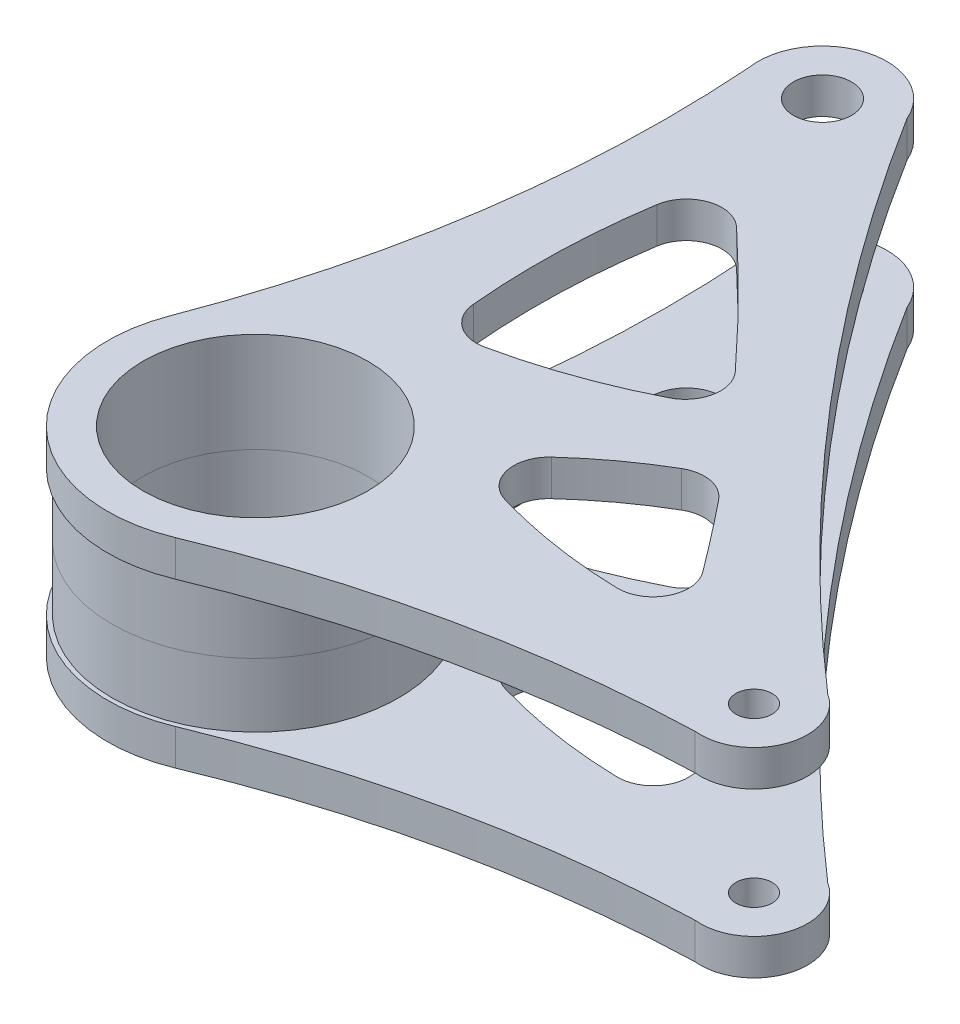
SolidWorks part; units mm, degrees
ref_plane "Front Plane" through (0, 0, 0) normal (0, 0, 1) x (1, 0, 0)
ref_plane "Top Plane" through (0, 0, 0) normal (0, 1, 0) x (1, 0, 0)
ref_plane "Right Plane" through (0, 0, 0) normal (1, 0, 0) x (0, 0, -1)
sketch "Sketch1" plane through (0, 0, 0) normal (0, 1, 0) x (1, 0, 0)
  line L0 (0, 80) -> (0, 0) construction
  line L1 (-9.0011, 81.338) -> (-20.6356, 3.0674)
  line L2 (6.9286, 85.8995) -> (74.8576, 6.1217)
  line L3 (4.3808, -20.3972) -> (70.6945, -6.1546)
  circle A0 centre (0, 0) radius 15.8623
  circle A1 centre (0, 80) radius 4.1
  circle A2 centre (69.1091, 1.2271) radius 2.55
  circle A3 centre (0, 80) radius 9.1
  circle A4 centre (0, 0) radius 20.8623
  circle A5 centre (69.1091, 1.2271) radius 7.55
  point P5 (0, 0)
  point P19 (59.8369, -10.5148)
  point P20 (60.48, 0)
  dimension "D1" = 8.2
  dimension "1" = 31.7246
  dimension "D3" = 5.1
  dimension "D5" = 69.12
  dimension "D4" = 80
  dimension "D6" = 5
extrude "Boss-Extrude1" add sketch "Sketch1" along normal blind 5.08 contours A1 A3 | A3 L0 A4 L3 A5 L2 | A4 A0 | L0 A3 L1 A4 | A5 A2 region at (-6.6966, 0, -74.2253) region at (29.5673, 0, -26.3622) region at (-7.9105, 0, -42.4424) region at (14.3346, 0, -14.3346) region at (75.994, 0, -3.7611)
sketch "Sketch3" plane through (0, 5.08, 0) normal (0, 1, 0) x (1, 0, 0)
  line L23 (6.9286, 85.8995) -> (74.8576, 6.1217) construction
  line L24 (6.9286, 85.8995) -> (74.8576, 6.1217)
  circle A29 centre (0, 80) radius 9.1
  circle A30 centre (0, 0) radius 20.8623
  circle A31 centre (69.1091, 1.2271) radius 7.55
  arc A32 (1.124, 24.8547) -> (31.4163, 35.8255) centre (-9.9767, 102.8121) ccw
  arc A33 (-9.1, 80) -> (-19.488, 7.4468) centre (-174.4184, 66.6496) cw
  arc A34 (7.9798, -19.2758) -> (68.3218, -6.2818) centre (73.7743, -178.2079) cw
  arc A35 (70.6945, -6.1546) -> (74.8576, 6.1217) centre (69.1091, 1.2271) ccw construction
  arc A36 (-20.6356, 3.0674) -> (4.3808, -20.3972) centre (0, 0) ccw construction
  arc A37 (6.9286, 85.8995) -> (-9.0011, 81.338) centre (0, 80) ccw construction
  arc A38 (3.0418, 64.268) -> (1.799, 20.7846) centre (102.9531, 39.6531) ccw
  arc A39 (3.0418, 64.268) -> (54.8896, 6.1217) centre (-221.7632, -188.3747) cw
  arc A40 (16.9411, 12.1752) -> (66.9551, 8.4633) centre (47.0346, 78.8536) ccw
  arc A41 (39.0442, 26.9044) -> (19.0809, 11.2502) centre (66.1753, -28.2515) ccw
  arc A42 (6.9286, 85.8995) -> (74.8576, 6.1217) centre (295.1167, 262.4762) ccw
  point P29 (3.0418, 64.268)
  point P32 (16.9411, 12.1752)
  point P36 (0, 0)
  point P40 (56.5898, 5.8028)
  point P41 (54.8896, 6.1217)
  line M15 (-9.0011, 81.338) -> (-20.6356, 3.0674)
  line M17 (4.3808, -20.3972) -> (70.6945, -6.1546)
  line M19 (74.8576, 6.1217) -> (6.9286, 85.8995)
extrude "Cut-Extrude1" cut sketch "Sketch3" against normal through all contours A33 A29 A30 M15 | A39 A29 A38 A32 | A39 A41 A40 | A34 A30 A31 M17 | A29 A42 A31 M19 region at (39.6539, 5.08, -44.9415) region at (-12.9781, 5.08, -42.6179) region at (38.0045, 5.08, 11.8867) region at (37.1781, 5.08, -14.1079) region at (11.4604, 5.08, -41.4426)
fillet "Fillet1" radius 5 6 edges at (54.8896, 2.54, -6.1217) (19.0809, 2.54, -11.2502) (39.0442, 2.54, -26.9044) (31.4163, 2.54, -35.8255) (1.124, 2.54, -24.8547) (3.0418, 2.54, -64.268)
sketch "Sketch2" plane through (0, 5.08, 0) normal (0, 1, 0) x (1, 0, 0)
  circle A7 centre (0, 0) radius 15.25
  circle A8 centre (0, 0) radius 20.25
  arc A9 (68.3218, -6.2818) -> (7.9798, -19.2758) centre (73.7743, -178.2079) ccw construction
  arc A10 (-19.488, 7.4468) -> (-8.994, 78.615) centre (-174.4184, 66.6496) ccw construction
  arc A11 (68.3218, -6.2818) -> (7.9798, -19.2758) centre (73.7743, -178.2079) ccw
  arc A12 (-19.488, 7.4468) -> (-8.994, 78.615) centre (-174.4184, 66.6496) ccw
  arc M7 (-19.488, 7.4468) -> (7.9798, -19.2758) centre (0, 0) ccw
  circle M14 centre (0, 0) radius 15.8623
extrude "Boss-Extrude2" add sketch "Sketch2" along normal blind 9 contours A8 M7 M14 region at (-19.6772, 5.08, 0)
mirror "Mirror1" about plane through (0, 14.08, 0) normal (0, 1, 0) of bodies 102
ref_plane "Plane1" through (0, 14.08, 0) normal (0, -1, 0) x (-1, 0, 0)
ref_axis "Axis1" through (69.1091, 5.08, -1.2271) along (0, -1, 0)
ref_point "Pushrod Pt"
sketch "Sketch4" plane through (0, 14.08, 0) normal (0, -1, 0) x (-1, 0, 0)
  line L0 (0, 80) -> (0, 0)
  line L1 (0, 0) -> (-69.1091, 1.2271)
  line L2 (-69.1091, 1.2271) -> (0, 80)
sketch "Sketch5" plane through (0, 28.16, 0) normal (0, 1, 0) x (1, 0, 0)
  arc A0 (8.3738, 83.5622) -> (-8.994, 78.615) centre (0, 80) ccw construction
  arc A1 (-19.488, 7.4468) -> (7.9798, -19.2758) centre (0, 0) ccw construction
  point P0 (0, 89.1)
  point P1 (0, -20.8623)
  point P5 (76.7063, 1.2271)
  point P9 (-20.8623, 0)
  dimension "D1" = 109.9623
  dimension "D2" = 97.5686
